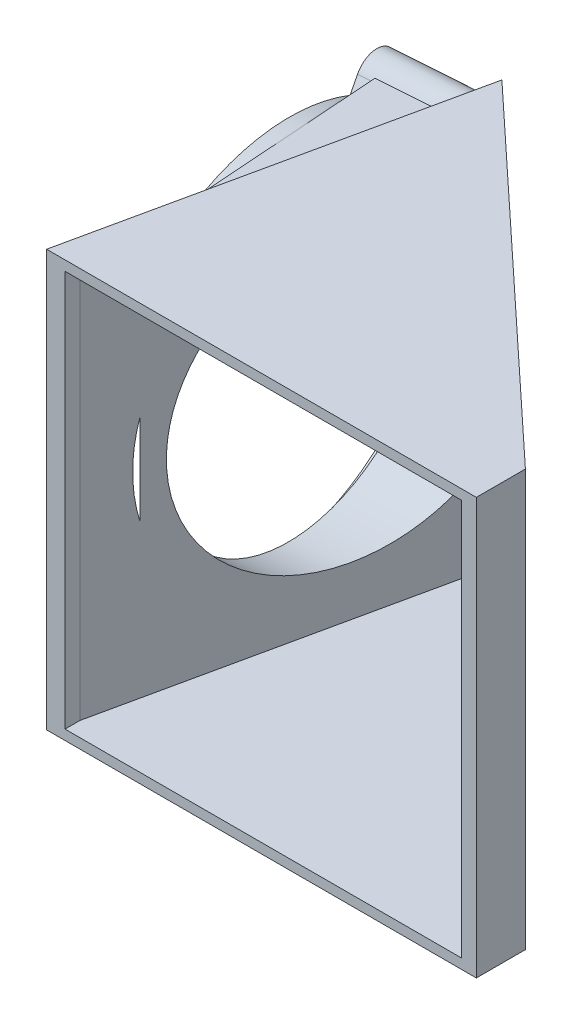
SolidWorks part; units mm, degrees
ref_plane "前视基准面" through (0, 0, 0) normal (0, 0, 1) x (1, 0, 0)
ref_plane "上视基准面" through (0, 0, 0) normal (0, 1, 0) x (1, 0, 0)
ref_plane "右视基准面" through (0, 0, 0) normal (1, 0, 0) x (0, 0, -1)
other "Configuration Table"
sketch "草图1" plane through (0, 0, 0) normal (0, 1, 0) x (1, 0, 0)
  line L0 (0, 0) -> (80, 0)
  line L1 (40, 0) -> (40, 47) construction
  line L2 (0, 84.3006) -> (90.4013, 0) construction
  line L3 (40, 47) -> (-39.8051, 41.4195) construction
  line L4 (84.0953, 90.1811) -> (89.6758, 10.376)
  line L5 (-40.6771, 53.889) -> (-38.9332, 28.9499)
  line L6 (-40.6771, 53.889) -> (84.0953, 90.1811) construction
  line L7 (-38.9332, 28.9499) -> (89.6758, 10.376) construction
  line L8 (-40.6771, 53.889) -> (80, 0) construction
  line L9 (15.1874, 70.1381) -> (0, 0)
  line L10 (-29.927, 72.1835) -> (-25.7417, 12.3296)
  line L11 (-25.7417, 12.3296) -> (-85.5955, 8.1442)
  line L12 (-85.5955, 8.1442) -> (-89.7809, 67.9981)
  line L13 (-89.7809, 67.9981) -> (-29.927, 72.1835)
  line L14 (-40.6771, 53.889) -> (141.1725, 0) construction
  line L15 (82.7001, 110.1324) -> (91.0709, -9.5753) construction
  line L16 (40, 47) -> (86.8855, 50.2786) construction
  line L17 (-25.7417, 12.3296) -> (3.1066, 14.3469) construction
  line L18 (-38.9332, 28.9499) -> (91.0709, -9.5753) construction
  line L19 (-39.4086, 35.7495) -> (81.2288, 0) construction
  point P15 (-27.8344, 42.2566)
  point P22 (4.898, 22.6198)
  dimension "D1" = 80
  dimension "D2" = 47
  dimension "D3" = 47
  dimension "D4" = 80
  dimension "D5" = 25
  dimension "D6" = 60
  dimension "D7" = 60
  dimension "D8" = 12
  dimension "D9" = 127
  dimension "D10" = 115
  dimension "D11" = 120
  dimension "D13" = 28.9187
sketch "草图2" plane through (0, 0, 0) normal (0, 1, 0) x (1, 0, 0)
  line L0 (-84.9158, 30) -> (133.106, 30) construction
  line L1 (0, 0) -> (80, 0) construction
  dimension "D1" = 30
sketch "草图3" plane through (0, 0, 0) normal (0, 1, 0) x (1, 0, 0)
  line L0 (15.1874, 70.1381) -> (0, 0)
  line L1 (0, 0) -> (80, 0)
  line L2 (80, 0) -> (80, 9.6994)
  line L3 (0, 84.3006) -> (90.4013, 0) construction
  line L6 (12.6335, 72.5196) -> (-3.7191, -3)
  line L7 (-3.7191, -3) -> (83, -3)
  line L8 (83, -3) -> (83, 6.9019)
  line L9 (12.6335, 72.5196) -> (15.1874, 70.1381)
  line L10 (13.3725, 75.9325) -> (-3.7191, -3) construction
  line L11 (83, -3) -> (83, 11.0038) construction
  line L12 (83, 11.0038) -> (13.3725, 75.9325) construction
  line L13 (80, 9.6994) -> (83, 6.9019)
  line L14 (80, 9.6994) -> (15.1874, 70.1381) construction
  dimension "D1" = 3
extrude "凸台-拉伸1" add sketch "草图3" along normal blind 40 and the other way blind 40
sketch "草图4" plane through (0, -40, 0) normal (0, -1, 0) x (1, 0, 0)
  line L0 (12.6335, -72.5196) -> (83, -6.9019)
  line L1 (83, -6.9019) -> (83, 3)
  line L2 (83, 3) -> (-3.7191, 3)
  line L3 (-3.7191, 3) -> (12.6335, -72.5196)
extrude "凸台-拉伸2" add sketch "草图4" along normal blind 2
mirror "镜向1" about plane through (0, 0, 0) normal (0, 1, 0) of "凸台-拉伸2"
sketch "草图5" plane through (0, 0, 0) normal (0, 0, -1) x (-1, 0, 0)
  line L4 (0, -40) -> (0, 40)
  line L5 (0, 40) -> (-80, 40)
  line L6 (-80, 40) -> (-80, -40)
  line L7 (-80, -40) -> (0, -40)
  line L8 (0, -40) -> (0, 40)
  line L9 (0, 40) -> (-80, 40)
  line L10 (-80, 40) -> (-80, -40)
  line L11 (-80, -40) -> (0, -40)
  dimension "D1" = 0
extrude "切除-拉伸1" cut sketch "草图5" against normal up to next
sketch "草图7" plane through (0, 0, 0) normal (0, 1, 0) x (1, 0, 0)
  line L0 (0.6586, 17.2174) -> (11.9115, 69.1853)
  line L1 (-38.9332, 28.9499) -> (91.0709, -9.5753) construction
  line L2 (-3.7191, -3) -> (12.6335, 72.5196) construction
  line L3 (-40.6771, 53.889) -> (84.0953, 90.1811) construction
  line L4 (11.9115, 69.1853) -> (-2.6786, 64.9415)
  line L5 (-2.6786, 64.9415) -> (0.6586, 17.2174)
  line L6 (-40.6771, 53.889) -> (-38.9332, 28.9499) construction
extrude "凸台-拉伸3" add sketch "草图7" along normal blind 40 and the other way blind 40
sketch "草图8" plane through (1.8535, 0, -0.1296) normal (-0.9976, 0, 0.0698) x (0.0698, 0, 0.9976)
  circle A0 centre (-44.0953, 0) radius 35.5
  point P2 (0, 0)
  dimension "D1" = 71
extrude "切除-拉伸2" cut sketch "草图8" against normal blind 1 and the other way up to next
sketch "草图9" plane through (1.8535, 0, -0.1296) normal (-0.9976, 0, 0.0698) x (0.0698, 0, 0.9976)
  line L0 (-64.9702, 40) -> (-17.1295, 40) construction
  circle A0 centre (-44.0953, 0) radius 35.5
  circle A1 centre (-44.0953, 0) radius 40
extrude "凸台-拉伸4" add sketch "草图9" along normal blind 3
sketch "草图10" plane through (0, 0, 0) normal (0.9773, 0, 0.2116) x (0.2116, 0, -0.9773)
  line L4 (71.7636, -40) -> (71.7636, 40)
  line L5 (71.7636, 40) -> (0, 40)
  line L6 (0, 40) -> (0, -40)
  line L7 (0, -40) -> (71.7636, -40)
  line L8 (71.7636, -40) -> (71.7636, 40)
  line L9 (71.7636, 40) -> (0, 40)
  line L10 (0, 40) -> (0, -40)
  line L11 (0, -40) -> (71.7636, -40)
  dimension "D1" = 0
extrude "切除-拉伸3" cut sketch "草图10" along normal up to next
sketch "草图11" plane through (-1.1392, 0, 0.0797) normal (-0.9976, 0, 0.0698) x (0.0698, 0, 0.9976)
  circle A0 centre (-44.0953, 0) radius 30
  dimension "D1" = 60
extrude "切除-拉伸4" cut sketch "草图11" against normal up to next
sketch "草图12" plane through (-1.1392, 0, 0.0797) normal (-0.9976, 0, 0.0698) x (0.0698, 0, 0.9976)
  line L0 (-44.0953, 0) -> (-65.5953, 37.2391) construction
  line L1 (-104.0953, 0) -> (15.9047, 0) construction
  line L2 (-65.5953, 37.2391) -> (-64.0953, 34.641) construction
  line L3 (-61.6981, 39.4891) -> (-60.1981, 36.891)
  line L4 (-69.4924, 34.9891) -> (-67.9924, 32.391)
  line L5 (-44.0953, 0) -> (-17.6218, 33.8845) construction
  line L6 (-17.6218, 33.8845) -> (-19.4688, 31.5204) construction
  line L7 (-14.0758, 31.114) -> (-15.9227, 28.75)
  line L8 (-21.1679, 36.6549) -> (-23.0148, 34.2909)
  line L9 (-84.0953, 0) -> (0, 0) construction
  line L10 (-17.6218, -33.8845) -> (-19.4688, -31.5204) construction
  line L11 (-14.0758, -31.114) -> (-15.9227, -28.75)
  line L12 (-21.1679, -36.6549) -> (-23.0148, -34.2909)
  line L13 (-65.5953, -37.2391) -> (-64.0953, -34.641) construction
  line L14 (-61.6981, -39.4891) -> (-60.1981, -36.891)
  line L15 (-69.4924, -34.9891) -> (-67.9924, -32.391)
  circle A0 centre (-65.5953, 37.2391) radius 2.05
  arc A1 (-44.0953, 40) -> (-64.9702, 34.1209) centre (-44.0953, 0) ccw construction
  arc A2 (-6.8155, 14.4989) -> (-6.8155, -14.4989) centre (-44.0953, 0) ccw construction
  arc A3 (-61.6981, 39.4891) -> (-69.4924, 34.9891) centre (-65.5953, 37.2391) ccw
  arc A4 (-67.9924, 32.391) -> (-60.1981, 36.891) centre (-64.0953, 34.641) ccw
  arc A5 (-17.1295, 29.544) -> (-44.0953, 40) centre (-44.0953, 0) ccw construction
  arc A6 (-14.0758, 31.114) -> (-21.1679, 36.6549) centre (-17.6218, 33.8845) ccw
  arc A7 (-23.0148, 34.2909) -> (-15.9227, 28.75) centre (-19.4688, 31.5204) ccw
  circle A8 centre (-17.6218, 33.8845) radius 2.05
  circle A9 centre (-17.6218, -33.8845) radius 2.05
  circle A10 centre (-65.5953, -37.2391) radius 2.05
  arc A11 (-14.0758, -31.114) -> (-21.1679, -36.6549) centre (-17.6218, -33.8845) cw
  arc A12 (-23.0148, -34.2909) -> (-15.9227, -28.75) centre (-19.4688, -31.5204) cw
  arc A13 (-61.6981, -39.4891) -> (-69.4924, -34.9891) centre (-65.5953, -37.2391) cw
  arc A14 (-67.9924, -32.391) -> (-60.1981, -36.891) centre (-64.0953, -34.641) cw
  point P6 (-64.8453, 35.9401)
  point P18 (-18.5453, 32.7024)
  point P38 (-18.5453, -32.7024)
  point P44 (-64.8453, -35.9401)
  dimension "D3" = 4.5
  dimension "D4" = 4.1
  dimension "D7" = 4.1
  dimension "D8" = 4.5
  dimension "D1" = 43
  dimension "D2" = 60
  dimension "D5" = 52
  dimension "D6" = 43
extrude "凸台-拉伸5" add sketch "草图12" against normal up to next
sketch "草图13" plane through (-1.1392, 0, 0.0797) normal (-0.9976, 0, 0.0698) x (0.0698, 0, 0.9976)
  circle A0 centre (-65.5953, -37.2391) radius 2.05 construction
  circle A1 centre (-17.6218, -33.8845) radius 2.05 construction
  circle A2 centre (-17.6218, 33.8845) radius 2.05 construction
  circle A3 centre (-65.5953, 37.2391) radius 2.05 construction
  circle A4 centre (-65.5953, -37.2391) radius 2.05
  circle A5 centre (-17.6218, -33.8845) radius 2.05
  circle A6 centre (-17.6218, 33.8845) radius 2.05
  circle A7 centre (-65.5953, 37.2391) radius 2.05
extrude "切除-拉伸5" cut sketch "草图13" against normal blind 5
